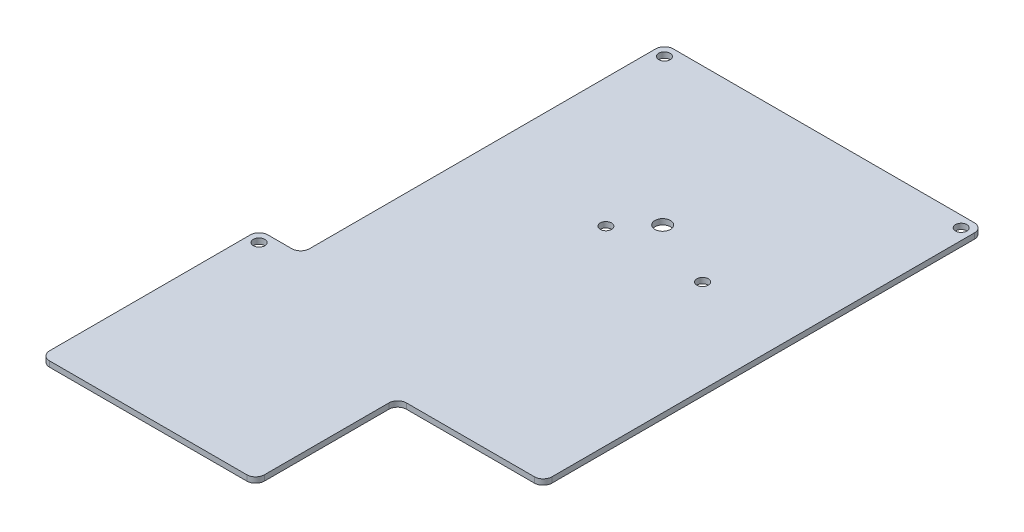
SolidWorks part; units mm, degrees
ref_plane "Front" through (0, 0, 0) normal (0, 0, 1) x (1, 0, 0)
ref_plane "Top" through (0, 0, 0) normal (0, 1, 0) x (1, 0, 0)
ref_plane "Right" through (0, 0, 0) normal (1, 0, 0) x (0, 0, -1)
sketch "Sketch1" plane through (0, 0, 0) normal (0, 1, 0) x (1, 0, 0)
  line L1 (-46, -63.5) -> (46, -63.5)
  line L2 (-46, -63.5) -> (-46, 63.5)
  line L3 (-46, 63.5) -> (46, 63.5)
  line L4 (46, -63.5) -> (46, 63.5)
  line L5 (-46, -63.5) -> (46, 63.5) construction
  line L6 (-46, 63.5) -> (46, -63.5) construction
  point P0 (0, 0)
  dimension "D1" = 127
  dimension "D2" = 92
extrude "Boss-Extrude1" add sketch "Sketch1" along normal blind 1.6
hole_wizard "#4 Clearance Hole1" positions "Sketch4" profile "Sketch5" hole size "#4" standard "ANSI Inch"
sketch "Sketch4" plane through (0, 1.6, 0) normal (0, 1, 0) x (1, 0, 0)
  line L2 (46, 63.5) -> (-46, 63.5) construction
  line L3 (-46, 63.5) -> (-46, -63.5) construction
  line L4 (-8.85, 9.46) -> (19.05, 9.46)
  point P22 (19.05, 9.46)
  point P24 (-8.85, 9.46)
  dimension "D1" = 27.9
  dimension "D3" = 54.04
  dimension "D4" = 37.15
sketch "Sketch5" plane through (19.05, 1.6, -9.46) normal (1, 0, 0) x (0, 0, 1)
  line L0 (0, 0) -> (0, 19.7306)
  line L1 (0, 19.7306) -> (1.6319, 18.75)
  line L2 (1.6319, 18.75) -> (1.6319, 0)
  line L5 (1.6319, 0) -> (0, 0)
  line L10 (0, 19.7306) -> (-1.632, 18.75) construction
  line L11 (0, -6.35) -> (0, 107.95) construction
  dimension "Hole Dia." = 3.2639
  dimension "Hole Depth" = 18.75
  dimension "Drill Angle" = 118
hole_wizard "#8 Clearance Hole1" positions "Sketch6" profile "Sketch7" hole size "#8" standard "ANSI Inch"
sketch "Sketch6" plane through (0, 0, 0) normal (0, -1, 0) x (-1, 0, 0)
  circle A1 centre (0.9676, 17.9647) radius 1.524 construction
  point P0 (0.9676, 17.9647)
sketch "Sketch7" plane through (-0.9676, 0, -17.9647) normal (1, 0, 0) x (0, 0, -1)
  line L0 (0, 0) -> (0, 20.1007)
  line L1 (0, 20.1007) -> (2.2479, 18.75)
  line L2 (2.2479, 18.75) -> (2.2479, 0)
  line L5 (2.2479, 0) -> (0, 0)
  line L10 (0, 20.1007) -> (-2.2479, 18.75) construction
  line L11 (0, -6.35) -> (0, 107.95) construction
  dimension "Hole Dia." = 4.4958
  dimension "Hole Depth" = 18.75
  dimension "Drill Angle" = 118
sketch "Sketch8" plane through (0, 0, 0) normal (0, 1, 0) x (1, 0, 0)
  line L0 (-46, -63.5) -> (46, -63.5) construction
  line L1 (4, -41.5) -> (-58, -41.5)
  line L2 (4, -41.5) -> (4, -104.5)
  line L3 (4, -104.5) -> (-58, -104.5)
  line L4 (-58, -41.5) -> (-58, -104.5)
  line L5 (4, -41.5) -> (-58, -104.5) construction
  line L6 (4, -104.5) -> (-58, -41.5) construction
  line L7 (-46, 63.5) -> (-46, -63.5) construction
  point P0 (-27, -73)
  dimension "D1" = 22
  dimension "D2" = 50
  dimension "D3" = 62
  dimension "D4" = 63
extrude "Boss-Extrude2" add sketch "Sketch8" along normal blind 1.6
hole_wizard "#4 Clearance Hole2" positions "Sketch2" profile "Sketch3" hole size "#4" standard "ANSI Inch"
sketch "Sketch2" plane through (0, 1.6, 0) normal (0, 1, 0) x (1, 0, 0)
  line L1 (-42.825, 60.325) -> (42.825, 60.325)
  line L2 (-42.825, 60.325) -> (-42.825, -60.325)
  line L3 (-42.825, -60.325) -> (42.825, -60.325)
  line L4 (42.825, 60.325) -> (42.825, -60.325)
  line L5 (-42.825, 60.325) -> (42.825, -60.325) construction
  line L6 (-42.825, -60.325) -> (42.825, 60.325) construction
  line L9 (46, -63.5) -> (46, 63.5) construction
  line L10 (4, -63.5) -> (46, -63.5) construction
  line L11 (-46, -41.5) -> (-58, -41.5) construction
  line L12 (-58, -41.5) -> (-58, -104.5) construction
  point P0 (-42.825, 60.325)
  point P2 (42.825, 60.325)
  point P118 (-54.82, -44.68)
  dimension "D1" = 3.175
  dimension "D2" = 3.175
  dimension "D3" = 3.18
  dimension "D4" = 3.18
sketch "Sketch3" plane through (-42.825, 1.6, -60.325) normal (1, 0, 0) x (0, 0, 1)
  line L0 (0, 0) -> (0, 50.9806)
  line L1 (0, 50.9806) -> (1.6319, 50)
  line L2 (1.6319, 50) -> (1.6319, 0)
  line L5 (1.6319, 0) -> (0, 0)
  line L10 (0, 50.9806) -> (-1.632, 50) construction
  line L11 (0, -6.35) -> (0, 107.95) construction
  dimension "Hole Dia." = 3.2639
  dimension "Hole Depth" = 50
  dimension "Drill Angle" = 118
fillet "Fillet1" radius 2.54 8 edges at (46, 0.8, 63.5) (46, 0.8, -63.5) (-46, 0.8, -63.5) (4, 0.8, 63.5) (4, 0.8, 104.5) (-58, 0.8, 104.5) (-58, 0.8, 41.5) (-46, 0.8, 41.5)
ref_point "PCB_ORIGIN"
sketch "TOP_KEEPOUT" plane through (0, 1.6, 0) normal (0, 1, 0) x (1, 0, 0)
  circle A0 centre (-8.85, 9.46) radius 3.429
  circle A1 centre (19.05, 9.46) radius 3.429
  circle A2 centre (42.825, 60.325) radius 3.429
  circle A3 centre (-42.825, 60.325) radius 3.429
  circle A6 centre (-54.82, -44.68) radius 3.429
  dimension "D1" = 6.858
sketch "BOTTOM_KEEPOUT" plane through (0, 0, 0) normal (0, -1, 0) x (1, 0, 0)
  line L1 (26.67, -45.02) -> (-26.7462, -45.02)
  line L2 (26.67, -45.02) -> (26.67, 56.58)
  line L3 (26.67, 56.58) -> (-26.7462, 56.58)
  line L4 (-26.7462, -45.02) -> (-26.7462, 56.58)
  line L5 (26.67, -41.464) -> (26.67, 55.056) construction
  line L6 (25.146, 56.58) -> (-25.2222, 56.58) construction
  line L8 (-26.7462, 55.056) -> (-26.7462, -40.7166) construction
  line L13 (-11.5062, -45.02) -> (23.114, -45.02) construction
  circle A2 centre (42.825, -60.325) radius 3.937
  circle A3 centre (-42.825, -60.325) radius 3.937
  circle A4 centre (-54.82, 44.68) radius 3.937
  dimension "D1" = 7.874
sketch "ARDUINO_MEGA_POSITIONS" plane through (0, 1.6, 0) normal (0, 1, 0) x (1, 0, 0)
  line L4 (22.86, -9.59) -> (22.86, -24.83) construction
  line L48 (22.86, -24.83) -> (25.4, -24.83) construction
  line L49 (25.4, -24.83) -> (25.4, -9.59) construction
  line L50 (23.622, -23.052) -> (23.622, -24.068) construction
  line L52 (23.622, -24.068) -> (24.638, -24.068) construction
  line L54 (24.638, -24.068) -> (24.638, -23.052) construction
  line L56 (22.86, -9.59) -> (22.86, -24.83)
  line L58 (22.86, -24.83) -> (25.4, -24.83)
  line L60 (25.4, -24.83) -> (25.4, -9.59)
  line L62 (23.622, -23.052) -> (23.622, -24.068)
  line L63 (23.622, -24.068) -> (24.638, -24.068)
  line L64 (24.638, -24.068) -> (24.638, -23.052)
  line L65 (-25.4762, -13.654) -> (-25.4762, -33.974) construction
  line L66 (-22.9362, -33.974) -> (-22.9362, -13.654) construction
  line L67 (-25.4762, -33.974) -> (-22.9362, -33.974) construction
  line L68 (-25.4762, -13.654) -> (-25.4762, -33.974)
  line L69 (-23.6982, -32.196) -> (-24.7142, -32.196)
  line L70 (-24.7142, -32.196) -> (-24.7142, -33.212)
  line L71 (-24.7142, -33.212) -> (-23.6982, -33.212)
  line L72 (-23.6982, -33.212) -> (-23.6982, -32.196)
  line L73 (-23.6982, -32.196) -> (-24.7142, -32.196)
  line L74 (-24.7142, -32.196) -> (-24.7142, -33.212)
  line L75 (-24.7142, -33.212) -> (-23.6982, -33.212)
  line L76 (-23.6982, -33.212) -> (-23.6982, -32.196)
  line L77 (-22.9362, -33.974) -> (-22.9362, -13.654)
  line L78 (-25.4762, -33.974) -> (-22.9362, -33.974)
  dimension "D1" = 0
